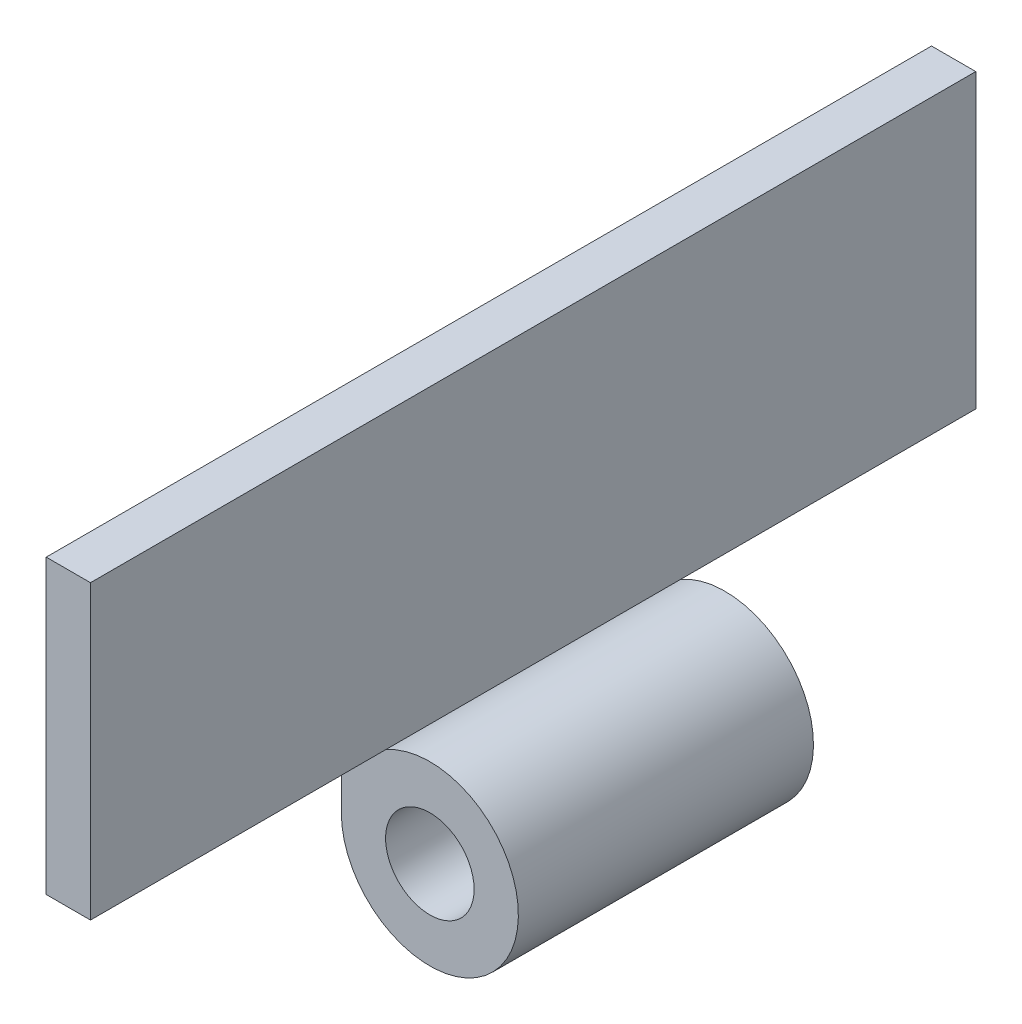
SolidWorks part; units mm, degrees
ref_plane "Front Plane" through (0, 0, 0) normal (0, 0, 1) x (1, 0, 0)
ref_plane "Top Plane" through (0, 0, 0) normal (0, 1, 0) x (1, 0, 0)
ref_plane "Right Plane" through (0, 0, 0) normal (1, 0, 0) x (0, 0, -1)
sketch "Sketch1" plane through (0, 0, 0) normal (0, 0, 1) x (1, 0, 0)
  line L0 (-6, 0) -> (-6, 25)
  line L1 (-6, 25) -> (-3, 25)
  line L2 (-3, 25) -> (-3, 5.1962)
  circle A0 centre (0, 0) radius 3
  arc A1 (-6, 0) -> (-3, 5.1962) centre (0, 0) ccw
  dimension "D1" = 3
  dimension "D2" = 6
  dimension "D3" = 3
  dimension "D4" = 25
extrude "Boss-Extrude1" add sketch "Sketch1" along normal blind 30 and the other way blind 30
sketch "Sketch2" plane through (0, 0, 30) normal (0, 0, 1) x (1, 0, 0)
  line L0 (-3, 5.1962) -> (-6, 5.1962)
  line L1 (-6, 25) -> (-6, 0) construction
  line L2 (-6, 5.1962) -> (-6, 0)
  arc A0 (-6, 0) -> (-3, 5.1962) centre (0, 0) ccw
extrude "Cut-Extrude1" cut sketch "Sketch2" against normal blind 20
mirror "Mirror1" about plane through (0, 0, 0) normal (0, 0, 1) of "Cut-Extrude1"
